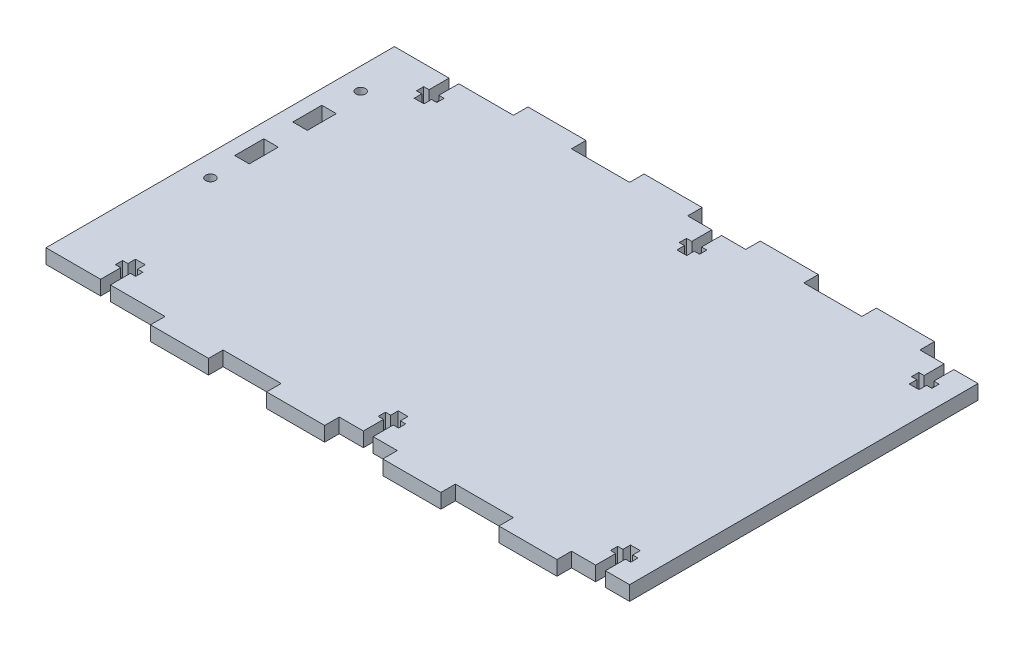
SolidWorks part; units mm, degrees
ref_plane "Front Plane" through (0, 0, 0) normal (0, 0, 1) x (1, 0, 0)
ref_plane "Top Plane" through (0, 0, 0) normal (0, 1, 0) x (1, 0, 0)
ref_plane "Right Plane" through (0, 0, 0) normal (1, 0, 0) x (0, 0, -1)
sketch "Sketch1" plane through (0, 0, 0) normal (0, 0, 1) x (1, 0, 0)
  line L0 (115.91, -15.875) -> (115.91, 155.575) construction
  line L1 (-139.3499, 155.575) -> (115.91, 155.575)
  line L2 (-139.3499, 155.575) -> (-139.3499, 149.225)
  line L3 (-139.3499, 149.225) -> (115.91, 149.225)
  line L4 (115.91, 155.575) -> (115.91, 149.225)
  dimension "D1" = 6.35
extrude "Boss-Extrude1" add sketch "Sketch1" along normal blind 152.4
sketch "Sketch2" plane through (0, 155.575, 0) normal (0, 1, 0) x (1, 0, 0)
  line L0 (90.51, 0) -> (90.51, 6.35)
  line L1 (115.91, 0) -> (-139.3499, 0) construction
  line L2 (-139.3499, 6.35) -> (-87.29, 6.35) construction
  line L3 (90.51, 6.35) -> (65.11, 6.35)
  line L4 (65.11, 6.35) -> (65.11, 0)
  line L5 (115.91, 0) -> (90.51, 0)
  line L6 (90.51, 0) -> (65.11, 0)
  line L9 (115.91, 0) -> (-139.3499, 0)
  line L10 (-139.3499, 0) -> (-139.3499, -152.4)
  line L11 (-139.3499, -152.4) -> (115.91, -152.4)
  line L12 (115.91, -152.4) -> (115.91, 0)
  line L13 (65.11, 0) -> (-139.3499, 0)
  line L14 (-139.3499, 0) -> (-139.3499, -152.4)
  line L15 (-139.3499, -152.4) -> (115.91, -152.4)
  line L16 (115.91, -152.4) -> (115.91, 0)
  line M7 (115.91, 0) -> (-139.3499, 0)
  dimension "D1" = 25.4
  dimension "D2" = 25.4
  dimension "D3" = 0
extrude "Boss-Extrude2" add sketch "Sketch2" against normal blind 6.35 contours L3 L4 L0 M7 region at (77.81, 155.575, -3.175)
pattern_linear "LPattern1" count 4 spacing 50.8 along (-1, 0, 0) of "Boss-Extrude2"
sketch "Sketch3" plane through (0, 0, 152.4) normal (0, 0, 1) x (1, 0, 0)
  line L0 (115.91, 155.575) -> (-139.3499, 155.575) construction
  line L1 (90.51, 155.575) -> (65.11, 155.575)
  line L2 (90.51, 155.575) -> (90.51, 149.225)
  line L3 (90.51, 149.225) -> (65.11, 149.225)
  line L4 (65.11, 155.575) -> (65.11, 149.225)
  line L5 (-139.3499, 149.225) -> (115.91, 149.225) construction
  dimension "D1" = 25.4
  dimension "D2" = 25.4
extrude "Boss-Extrude3" add sketch "Sketch3" along normal blind 6.35
pattern_linear "LPattern2" count 4 spacing 50.8 along (-1, 0, 0) of "Boss-Extrude3"
sketch "Sketch4" plane through (0, 155.575, 0) normal (0, 1, 0) x (1, 0, 0)
  line L0 (-139.3499, 0) -> (-87.29, 0) construction
  line L1 (90.51, 0) -> (115.91, 0) construction
  line L2 (-113.3199, 0) -> (-113.3199, -13.6148) construction
  line L3 (-87.29, 0) -> (-139.3499, 0) construction
  line L4 (1.61, 0) -> (1.61, -16.5479) construction
  line L5 (14.31, 0) -> (-11.09, 0) construction
  line L6 (103.21, 0) -> (103.21, -21.5198) construction
  line L7 (115.91, 0) -> (90.51, 0) construction
  line L8 (103.21, -152.4) -> (103.21, -137.4626) construction
  line L9 (115.91, -152.4) -> (90.51, -152.4) construction
  line L10 (1.61, -152.4) -> (1.61, -137.4626) construction
  line L11 (14.31, -152.4) -> (-11.09, -152.4) construction
  line L12 (-113.3199, -152.4) -> (-113.3199, -137.4626) construction
  line L13 (-87.29, -152.4) -> (-139.3499, -152.4) construction
  line L14 (-139.3499, -152.4) -> (115.91, -152.4) construction
  line L15 (-139.3499, -152.4) -> (115.91, -152.4) construction
  line B0 (-111.1863, 0) -> (-115.4535, 0)
  line B1 (-115.4535, -11.938) -> (-117.7649, -11.938)
  line B2 (-117.7649, -11.938) -> (-117.7649, -8.763)
  line B3 (-117.7649, -8.763) -> (-115.4535, -8.763)
  line B4 (-115.4535, -8.763) -> (-115.4535, 0)
  line B5 (-115.4535, -11.938) -> (-115.4535, -15.24)
  line B6 (-115.4535, -15.24) -> (-111.1863, -15.24)
  line B7 (-111.1863, -11.938) -> (-111.1863, -15.24)
  line B8 (-111.1863, -8.763) -> (-111.1863, 0)
  line B9 (-108.8749, -8.763) -> (-111.1863, -8.763)
  line B10 (-108.8749, -11.938) -> (-108.8749, -8.763)
  line B11 (-111.1863, -11.938) -> (-108.8749, -11.938)
  line B12 (3.7436, 0) -> (-0.5236, 0)
  line B13 (-0.5236, -11.938) -> (-2.835, -11.938)
  line B14 (-2.835, -11.938) -> (-2.835, -8.763)
  line B15 (-2.835, -8.763) -> (-0.5236, -8.763)
  line B16 (-0.5236, -8.763) -> (-0.5236, 0)
  line B17 (-0.5236, -11.938) -> (-0.5236, -15.24)
  line B18 (-0.5236, -15.24) -> (3.7436, -15.24)
  line B19 (3.7436, -11.938) -> (3.7436, -15.24)
  line B20 (3.7436, -8.763) -> (3.7436, 0)
  line B21 (6.055, -8.763) -> (3.7436, -8.763)
  line B22 (6.055, -11.938) -> (6.055, -8.763)
  line B23 (3.7436, -11.938) -> (6.055, -11.938)
  line B24 (105.3436, 0) -> (101.0764, 0)
  line B25 (101.0764, -11.938) -> (98.765, -11.938)
  line B26 (98.765, -11.938) -> (98.765, -8.763)
  line B27 (98.765, -8.763) -> (101.0764, -8.763)
  line B28 (101.0764, -8.763) -> (101.0764, 0)
  line B29 (101.0764, -11.938) -> (101.0764, -15.24)
  line B30 (101.0764, -15.24) -> (105.3436, -15.24)
  line B31 (105.3436, -11.938) -> (105.3436, -15.24)
  line B32 (105.3436, -8.763) -> (105.3436, 0)
  line B33 (107.655, -8.763) -> (105.3436, -8.763)
  line B34 (107.655, -11.938) -> (107.655, -8.763)
  line B35 (105.3436, -11.938) -> (107.655, -11.938)
  line B36 (-115.4535, -152.4) -> (-111.1863, -152.4)
  line B37 (-111.1863, -140.462) -> (-108.8749, -140.462)
  line B38 (-108.8749, -140.462) -> (-108.8749, -143.637)
  line B39 (-108.8749, -143.637) -> (-111.1863, -143.637)
  line B40 (-111.1863, -143.637) -> (-111.1863, -152.4)
  line B41 (-111.1863, -140.462) -> (-111.1863, -137.16)
  line B42 (-111.1863, -137.16) -> (-115.4535, -137.16)
  line B43 (-115.4535, -140.462) -> (-115.4535, -137.16)
  line B44 (-115.4535, -143.637) -> (-115.4535, -152.4)
  line B45 (-117.7649, -143.637) -> (-115.4535, -143.637)
  line B46 (-117.7649, -140.462) -> (-117.7649, -143.637)
  line B47 (-115.4535, -140.462) -> (-117.7649, -140.462)
  line B48 (-0.5236, -152.4) -> (3.7436, -152.4)
  line B49 (3.7436, -140.462) -> (6.055, -140.462)
  line B50 (6.055, -140.462) -> (6.055, -143.637)
  line B51 (6.055, -143.637) -> (3.7436, -143.637)
  line B52 (3.7436, -143.637) -> (3.7436, -152.4)
  line B53 (3.7436, -140.462) -> (3.7436, -137.16)
  line B54 (3.7436, -137.16) -> (-0.5236, -137.16)
  line B55 (-0.5236, -140.462) -> (-0.5236, -137.16)
  line B56 (-0.5236, -143.637) -> (-0.5236, -152.4)
  line B57 (-2.835, -143.637) -> (-0.5236, -143.637)
  line B58 (-2.835, -140.462) -> (-2.835, -143.637)
  line B59 (-0.5236, -140.462) -> (-2.835, -140.462)
  line B60 (101.0764, -152.4) -> (105.3436, -152.4)
  line B61 (105.3436, -140.462) -> (107.655, -140.462)
  line B62 (107.655, -140.462) -> (107.655, -143.637)
  line B63 (107.655, -143.637) -> (105.3436, -143.637)
  line B64 (105.3436, -143.637) -> (105.3436, -152.4)
  line B65 (105.3436, -140.462) -> (105.3436, -137.16)
  line B66 (105.3436, -137.16) -> (101.0764, -137.16)
  line B67 (101.0764, -140.462) -> (101.0764, -137.16)
  line B68 (101.0764, -143.637) -> (101.0764, -152.4)
  line B69 (98.765, -143.637) -> (101.0764, -143.637)
  line B70 (98.765, -140.462) -> (98.765, -143.637)
  line B71 (101.0764, -140.462) -> (98.765, -140.462)
sketch_block_instance "TSlot-1"
sketch_block "TSlot" parameters "D1"=3.302, "D2"=3.175
sketch_block_instance "TSlot-3"
sketch_block_instance "TSlot-4"
sketch_block_instance "TSlot-9"
sketch_block_instance "TSlot-11"
sketch_block_instance "TSlot-12"
extrude "Cut-Extrude1" cut sketch "Sketch4" against normal blind 6.35
sketch "Sketch5" plane through (0, 155.575, 0) normal (0, 1, 0) x (1, 0, 0)
  line L0 (-132.9999, -55.2358) -> (-132.9999, -140.7347) construction
  line L1 (-132.9999, -38.1) -> (-126.6499, -38.1)
  line L2 (-132.9999, -38.1) -> (-132.9999, -50.8)
  line L3 (-132.9999, -50.8) -> (-126.6499, -50.8)
  line L4 (-126.6499, -38.1) -> (-126.6499, -50.8)
  line L5 (-132.9999, -63.5) -> (-126.6499, -63.5)
  line L6 (-132.9999, -63.5) -> (-132.9999, -76.2)
  line L7 (-132.9999, -76.2) -> (-126.6499, -76.2)
  line L8 (-126.6499, -63.5) -> (-126.6499, -76.2)
  line L10 (-139.3499, -152.4) -> (-139.3499, 0) construction
  line L11 (-115.4535, 0) -> (-139.3499, 0) construction
  dimension "D1" = 12.7
  dimension "D2" = 6.35
  dimension "D3" = 6.35
  dimension "D4" = 12.7
  dimension "D5" = 12.7
  dimension "D6" = 6.35
  dimension "D7" = 38.1
extrude "Cut-Extrude2" cut sketch "Sketch5" against normal through all
sketch "Sketch6" plane through (0, 155.575, 0) normal (0, 1, 0) x (1, 0, 0)
  line L0 (-132.9999, -22.1864) -> (-126.6499, -26.4536) construction
  line L1 (-132.9999, -26.4536) -> (-126.6499, -22.1864) construction
  line L2 (-132.9999, -87.8464) -> (-126.6499, -92.1136) construction
  line L3 (-132.9999, -92.1136) -> (-126.6499, -87.8464) construction
  circle A0 centre (-129.8249, -89.98) radius 2.0955
  circle A1 centre (-129.8249, -24.32) radius 2.0955
  dimension "D1" = 4.191
extrude "Cut-Extrude3" cut sketch "Sketch6" against normal through all
